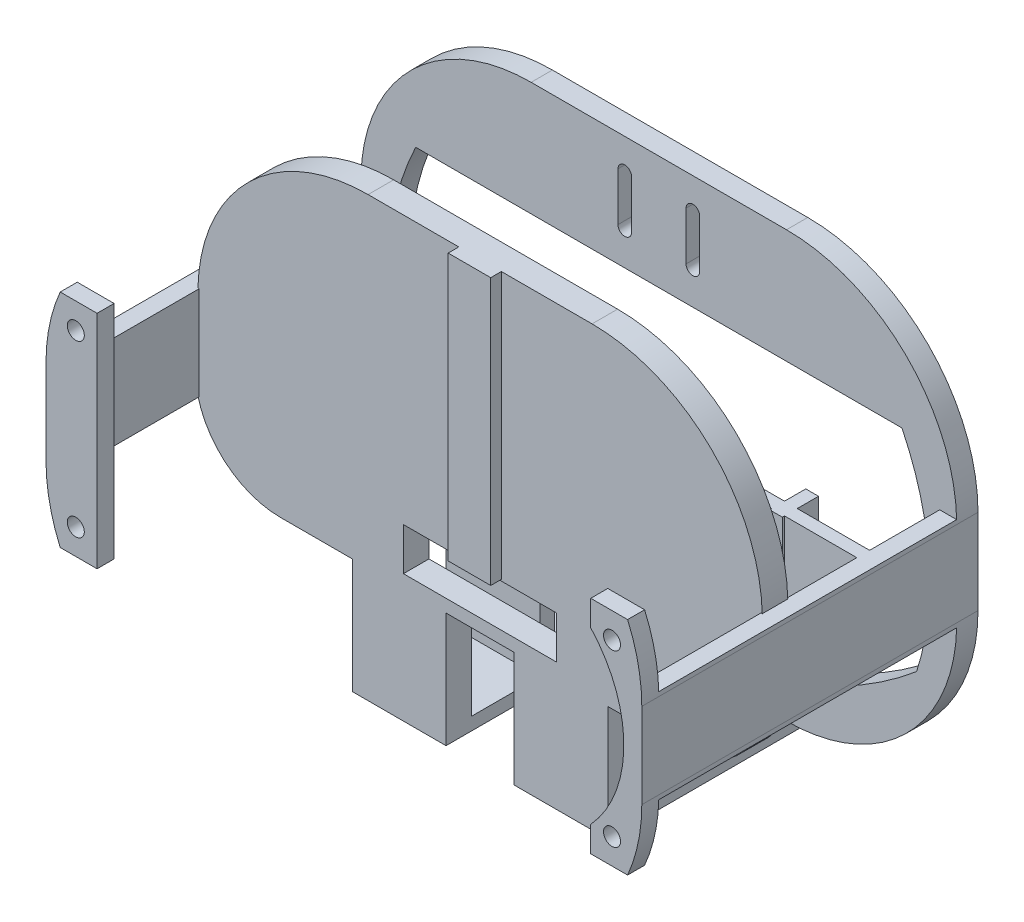
SolidWorks part; units mm, degrees
ref_plane "Front Plane" through (0, 0, 0) normal (0, 0, 1) x (1, 0, 0)
ref_plane "Top Plane" through (0, 0, 0) normal (0, 1, 0) x (1, 0, 0)
ref_plane "Right Plane" through (0, 0, 0) normal (1, 0, 0) x (0, 0, -1)
sketch "Sketch1" plane through (0, 0, 0) normal (0, 0, 1) x (1, 0, 0)
  line L1 (70, -50) -> (-70, -50)
  line L2 (70, -50) -> (70, 50)
  line L3 (70, 50) -> (-70, 50)
  line L4 (-70, -50) -> (-70, 50)
  line L5 (70, -50) -> (-70, 50) construction
  line L6 (70, 50) -> (-70, -50) construction
  point P0 (0, 0)
  dimension "D1" = 140
  dimension "D2" = 100
extrude "Boss-Extrude1" add sketch "Sketch1" along normal blind 5
sketch "Sketch2" plane through (0, 0, 5) normal (0, 0, 1) x (1, 0, 0)
  line L0 (-70, 0) -> (70, 0) construction
  line L1 (-70, 50) -> (-70, -50) construction
  line L2 (70, -50) -> (70, 50) construction
  line L3 (0, 50) -> (0, -50) construction
  line L4 (70, 50) -> (-70, 50) construction
  line L5 (-70, -50) -> (70, -50) construction
  line L6 (66, 26) -> (70, -26) construction
  line L7 (-66, -26) -> (-70, -26)
  line L8 (-66, -26) -> (-66, 26)
  line L9 (-66, 26) -> (-70, 26)
  line L10 (-70, -26) -> (-70, 26)
  line L11 (-66, -26) -> (-70, 26) construction
  line L12 (-66, 26) -> (-70, -26) construction
  line L13 (66, -26) -> (70, 26) construction
  line L14 (70, -26) -> (70, 26)
  line L15 (66, 26) -> (70, 26)
  line L16 (66, -26) -> (66, 26)
  line L17 (66, -26) -> (70, -26)
  point P12 (-68, 0)
  point P21 (68, 0)
  dimension "D1" = 4
  dimension "D2" = 0
  dimension "D3" = 52
extrude "Boss-Extrude2" add sketch "Sketch2" along normal blind 70
sketch "Sketch3" plane through (0, 0, 75) normal (0, 0, 1) x (1, 0, 0)
  line L0 (0, 50) -> (0, -50) construction
  line L1 (70, 50) -> (-70, 50) construction
  line L2 (-70, -50) -> (70, -50) construction
  line L4 (-70, 26) -> (-58, 26)
  line L5 (-70, 26) -> (-70, -26)
  line L6 (-70, -26) -> (-58, -26)
  line L7 (-58, 26) -> (-58, -26)
  line L8 (-70, -26) -> (-66, -26) construction
  line L9 (58, 26) -> (58, -26)
  line L10 (70, -26) -> (58, -26)
  line L11 (70, 26) -> (70, -26)
  line L12 (70, 26) -> (58, 26)
  dimension "D1" = 12
extrude "Boss-Extrude3" add sketch "Sketch3" along normal blind 4
sketch "Sketch4" plane through (0, 0, 79) normal (0, 0, 1) x (1, 0, 0)
  line L0 (-70, 0) -> (70, 0) construction
  line L1 (-70, 26) -> (-70, -26) construction
  line L2 (70, -26) -> (70, 26) construction
  line L3 (0, 50) -> (0, -50) construction
  line L4 (70, 50) -> (-70, 50) construction
  line L5 (-70, -50) -> (70, -50) construction
  circle A0 centre (-63, 20) radius 2
  circle A1 centre (-63, -20) radius 2
  circle A2 centre (63, 20) radius 2
  circle A3 centre (63, -20) radius 2
  dimension "D1" = 4
  dimension "D2" = 7
  dimension "D3" = 20
extrude "Cut-Extrude1" cut sketch "Sketch4" against normal blind 4
sketch "Sketch5" plane through (-70, 0, 0) normal (-1, 0, 0) x (0, 0, 1)
  line L0 (79, 26) -> (79, -26) construction
  line L1 (5, 26) -> (75, 26)
  line L2 (5, 26) -> (5, 11)
  line L3 (5, 11) -> (75, 11)
  line L4 (75, 26) -> (75, 11)
  line L5 (5, -26) -> (75, -26)
  line L6 (5, -26) -> (5, -11)
  line L7 (5, -11) -> (75, -11)
  line L8 (75, -26) -> (75, -11)
  dimension "D1" = 4
  dimension "D2" = 4
  dimension "D3" = 15
  dimension "D4" = 15
extrude "Cut-Extrude3" cut sketch "Sketch5" against normal through all
fillet "Fillet1" radius 40 4 edges at (70, -50, 2.5) (70, 50, 2.5) (-70, 50, 2.5) (-70, -50, 2.5)
sketch "Sketch9" plane through (0, 0, 0) normal (0, 0, -1) x (-1, 0, 0)
  line L0 (0, 50) -> (0, 23.9891) construction
  line L1 (-30, 50) -> (30, 50) construction
  line L2 (-8, 42.5954) -> (-8, 31.2501) construction
  line L3 (-6.4, 42.5954) -> (-6.4, 31.2501)
  line L4 (-9.6, 42.5954) -> (-9.6, 31.2501)
  line L5 (8, 42.5954) -> (8, 31.2501) construction
  line L6 (6.4, 42.5954) -> (6.4, 31.2501)
  line L7 (9.6, 42.5954) -> (9.6, 31.2501)
  arc A0 (-6.4, 42.5954) -> (-9.6, 42.5954) centre (-8, 42.5954) ccw
  arc A1 (-9.6, 31.2501) -> (-6.4, 31.2501) centre (-8, 31.2501) ccw
  arc A2 (6.4, 42.5954) -> (9.6, 42.5954) centre (8, 42.5954) cw
  arc A3 (9.6, 31.2501) -> (6.4, 31.2501) centre (8, 31.2501) cw
  point P7 (-8, 36.9227)
  point P14 (8, 36.9227)
  dimension "D2" = 1.6
  dimension "D1" = 8
extrude "Cut-Extrude6" cut sketch "Sketch9" against normal blind 10
sketch "Sketch11" plane through (0, -50, 0) normal (0, -1, 0) x (1, 0, 0)
  line L0 (0, 0) -> (0, 37.8621) construction
  line L1 (-30, 0) -> (-8, 0)
  line L2 (-30, 0) -> (-30, 41)
  line L3 (-30, 41) -> (-8, 41)
  line L4 (-8, 0) -> (-8, 41)
  line L6 (-30, 0) -> (30, 0) construction
  line L7 (8, 0) -> (8, 41)
  line L8 (30, 41) -> (8, 41)
  line L9 (30, 0) -> (30, 41)
  line L10 (30, 0) -> (8, 0)
  dimension "D1" = 22
  dimension "D2" = 41
extrude "Boss-Extrude6" add sketch "Sketch11" along normal blind 3
sketch "Sketch12" plane through (0, -53, 0) normal (0, -1, 0) x (1, 0, 0)
  line L0 (0, 60.22) -> (0, 0) construction
  line L1 (-30, 41) -> (-8, 41)
  line L2 (-30, 41) -> (-30, 47)
  line L3 (-30, 47) -> (-8, 47)
  line L4 (-8, 41) -> (-8, 47)
  line L5 (8, 41) -> (8, 47)
  line L6 (30, 47) -> (8, 47)
  line L7 (30, 41) -> (30, 47)
  line L8 (30, 41) -> (8, 41)
  dimension "D1" = 6
extrude "Boss-Extrude7" add sketch "Sketch12" against normal blind 30
sketch "Sketch15" plane through (0, 0, 47) normal (0, 0, 1) x (1, 0, 0)
  line L0 (-66.6606, -26) -> (-58, -26) construction
  line L1 (-66.3, -26) -> (66.3, -26)
  line L2 (-66.3, -26) -> (-66.3, 50)
  line L3 (-66.3, 50) -> (66.3, 50)
  line L4 (66.3, -26) -> (66.3, 50)
  line L7 (30, 50) -> (-30, 50) construction
  line L9 (70, -10) -> (70, 10) construction
  dimension "D1" = 0
  dimension "D2" = 0
  dimension "D3" = 3.7
  dimension "D4" = 3.7
extrude "Boss-Extrude8" add sketch "Sketch15" against normal blind 6
fillet "Fillet2" radius 40 2 edges at (66.3, 50, 44) (-66.3, 50, 44)
fillet "Fillet3" radius 20 2 edges at (66.3, -26, 44) (-66.3, -26, 44)
sketch "Sketch24" plane through (0, 0, 0) normal (0, 0, -1) x (-1, 0, 0)
  line L3 (57.1278, 23.2208) -> (-57.1278, 23.2208)
  line L5 (60.5793, -24.6237) -> (-57.1278, 23.2208) construction
  line L6 (57.1278, 23.2208) -> (-60.5793, -24.6237) construction
  arc A0 (-60.5793, -24.6237) -> (60.5793, -24.6237) centre (0, 47.1187) ccw
  arc A1 (-57.1278, 23.2208) -> (-60.5793, -24.6237) centre (0.6698, -4.9955) ccw
  arc A2 (57.1278, 23.2208) -> (60.5793, -24.6237) centre (-1.7816, -5.0757) cw
  point P0 (0, 0)
  point P9 (0, -46.7792)
  point P10 (-63.4808, -0.3677)
  point P11 (63.4019, -0.3733)
  dimension "D1" = 70
  dimension "D2" = 126.8828
extrude "Cut-Extrude13" cut sketch "Sketch24" against normal blind 10
sketch "Sketch25" plane through (0, 0, 47) normal (0, 0, 1) x (1, 0, 0)
  line L0 (0, 50) -> (0, -26) construction
  line L1 (26.3125, 50) -> (-26.3125, 50) construction
  line L2 (-8, -26) -> (8, -26) construction
  line L4 (-5, 50) -> (5, 50)
  line L5 (-5, 50) -> (-5, -12.6486)
  line L6 (-5, -12.6486) -> (5, -12.6486)
  line L7 (5, 50) -> (5, -12.6486)
  dimension "D1" = 5
  dimension "D2" = 5
extrude "Boss-Extrude9" add sketch "Sketch25" along normal blind 2.5
sketch "Sketch26" plane through (0, 0, 41) normal (0, 0, -1) x (-1, 0, 0)
  line L0 (0, 50) -> (0, -26) construction
  line L2 (-66, -11) -> (-66, 11)
  line L4 (66.3, -11) -> (66.3, 11)
  line L5 (-26.3125, 50) -> (26.3125, 50) construction
  line L6 (8, -26) -> (-8, -26) construction
  line L7 (-10.75, -11) -> (-10.75, -13)
  line L9 (10.75, -11) -> (10.75, 11)
  line L11 (-10.75, -11) -> (-10.75, 11)
  line L12 (10.75, -11) -> (-10.75, 11) construction
  line L13 (10.75, 11) -> (-10.75, -11) construction
  line L14 (13, -13) -> (10.75, -13)
  line L15 (13, -13) -> (13, 13)
  line L16 (13, 13) -> (10.75, 13)
  line L17 (-13, -13) -> (-13, 13)
  line L18 (13, -13) -> (-11.184, 11.184) construction
  line L19 (10.702, 10.702) -> (-13, -13) construction
  line L20 (-10.75, -13) -> (-10.75, 13)
  line L21 (10.75, 13) -> (10.75, -13)
  line L22 (-10.75, 13) -> (-13, 13)
  line L25 (-10.75, -13) -> (-13, -13)
  point P12 (0, 0)
  point P18 (0, 0)
  dimension "D1" = 21.5
  dimension "D2" = 22
  dimension "D3" = 26
  dimension "D4" = 26
  dimension "D5" = 10.75
extrude "Boss-Extrude10" add sketch "Sketch26" along normal blind 16 contours L25 L7 L11 L20 L22 L17 | L16 L21 L9 L14 L15 region at (11.875, 0, 41) region at (-11.875, 0, 41)
sketch "Sketch27" plane through (0, 13, 0) normal (0, 1, 0) x (1, 0, 0)
  line L0 (-10.75, -25) -> (-10.75, -41) construction
  line L1 (-10.75, -32.5) -> (10.75, -32.5)
  line L2 (-10.75, -32.5) -> (-10.75, -30)
  line L3 (-10.75, -30) -> (10.75, -30)
  line L4 (10.75, -32.5) -> (10.75, -30)
  line L5 (10.75, -25) -> (10.75, -41) construction
  line L6 (26.3125, -41) -> (-26.3125, -41) construction
  line L7 (-13, -25) -> (-10.75, -25) construction
  dimension "D1" = 8.5
  dimension "D2" = 2.5
  dimension "D3" = 5
extrude "Boss-Extrude11" add sketch "Sketch27" against normal blind 26
fillet "Fillet4" radius 5 2 edges at (13, 0, 41) (-13, 0, 41)
sketch "Sketch29" plane through (0, 0, 30) normal (0, 0, -1) x (-1, 0, 0)
  line L0 (-10.75, -13) -> (10.75, -13) construction
  line L1 (-10.75, -3) -> (3.25, -3)
  line L2 (-10.75, -3) -> (-10.75, -13)
  line L3 (-10.75, -13) -> (3.25, -13)
  line L4 (3.25, -3) -> (3.25, -13)
  line L5 (-10.75, -13) -> (-10.75, 13) construction
  dimension "D1" = 14
  dimension "D2" = 0
  dimension "D3" = 10
  dimension "D4" = 0
extrude "Cut-Extrude14" cut sketch "Sketch29" against normal blind 5
sketch "Sketch30" plane through (0, 0, 75) normal (0, 0, -1) x (-1, 0, 0)
  line L0 (-58, 26) -> (-58, -26) construction
  line L1 (-58, 20) -> (-58, -20)
  arc A0 (-58, 20) -> (-58, -20) centre (-36.1952, 0) ccw
extrude "Cut-Extrude15" cut sketch "Sketch30" against normal blind 5
sketch "Sketch33" plane through (0, 11, 0) normal (0, 1, 0) x (1, 0, 0)
  line L0 (-66, -5) -> (-66, -41) construction
  line L1 (-66, -25) -> (-30, -25)
  line L2 (-66, -25) -> (-66, -22)
  line L3 (-66, -22) -> (-30, -22)
  line L4 (-30, -25) -> (-30, -22)
  line L5 (66, -41) -> (66, -5) construction
  line L6 (66, -24.4737) -> (30, -24.4737)
  line L7 (66, -24.4737) -> (66, -21.4737)
  line L8 (66, -21.4737) -> (30, -21.4737)
  line L9 (30, -24.4737) -> (30, -21.4737)
  line L10 (-69.9875, -5) -> (-30, -5) construction
  point P12 (0, 0)
  point P14 (0, 0)
  dimension "D1" = 3
  dimension "D2" = 3
  dimension "D3" = 36
  dimension "D4" = 36
  dimension "D5" = 17
extrude "Boss-Extrude12" add sketch "Sketch33" against normal blind 22
sketch "Sketch34" plane through (0, 0, 21.4737) normal (0, 0, -1) x (-1, 0, 0)
  line L0 (-66, 11) -> (-30, 11) construction
  line L1 (46, -36) -> (-46, -36)
  line L2 (46, -36) -> (46, 36)
  line L3 (46, 36) -> (-46, 36)
  line L4 (-46, -36) -> (-46, 36)
  line L5 (46, -36) -> (-46, 36) construction
  line L6 (46, 36) -> (-46, -36) construction
  line L7 (-46, -11) -> (-49, -11)
  line L8 (-46, -11) -> (-46, 11)
  line L9 (-46, 11) -> (-49, 11)
  line L10 (-49, -11) -> (-49, 11)
  line L11 (30, 11) -> (66, 11) construction
  line L12 (46, 11) -> (49, 11)
  line L13 (46, 11) -> (46, -11)
  line L14 (46, -11) -> (49, -11)
  line L15 (49, 11) -> (49, -11)
  line L16 (30, -11) -> (66, -11) construction
  line L19 (-8, -26) -> (-8, -50) construction
  line L20 (-30, -50) -> (-8, -50)
  line L21 (-30, -50) -> (-30, -33)
  line L22 (-30, -33) -> (-8, -33)
  line L23 (-8, -50) -> (-8, -33)
  line L24 (30, -26) -> (30, -50) construction
  line L25 (8, -50) -> (30, -50)
  line L26 (8, -50) -> (8, -33)
  line L27 (8, -33) -> (30, -33)
  line L28 (30, -50) -> (30, -33)
  point P0 (0, 0)
  line M10 (-30, 11) -> (-66, 11)
  line M12 (-66, -11) -> (-30, -11)
  dimension "D1" = 92
  dimension "D2" = 72
  dimension "D3" = 3
  dimension "D4" = 3
  dimension "D5" = 0
  dimension "D6" = 22
  dimension "D7" = 17
  dimension "D8" = 17
extrude "Boss-Extrude13" add sketch "Sketch34" along normal blind 5 and the other way blind 3.5 contours L10 L4 M12 M10 | L15 L14 L13 L12 | L8 L7 L10 L9 | L21 L20 L23 L22 | L26 L25 L28 L27 region at (47.5, 0, 21.4737)
sketch "Sketch35" plane through (-30, 0, 0) normal (-1, 0, 0) x (0, 0, 1)
  line L0 (47, -53) -> (0, -53) construction
  line L1 (16.4737, -33) -> (21.4737, -33)
  line L2 (16.4737, -33) -> (16.4737, -50)
  line L3 (16.4737, -50) -> (21.4737, -50)
  line L4 (21.4737, -33) -> (21.4737, -50)
  line L6 (21.4737, -11) -> (21.4737, 11) construction
  dimension "D1" = 3
  dimension "D2" = 0
extrude "Cut-Extrude16" cut sketch "Sketch35" against normal through all
sketch "Sketch36" plane through (0, 0, 41) normal (0, 0, -1) x (-1, 0, 0)
  line L1 (-18, -13) -> (18.012, -13)
  line L2 (-18, -13) -> (-18, -23)
  line L3 (-18, -23) -> (18.012, -23)
  line L4 (18.012, -13) -> (18.012, -23)
  dimension "D1" = 10
extrude "Cut-Extrude17" cut sketch "Sketch36" against normal blind 8
